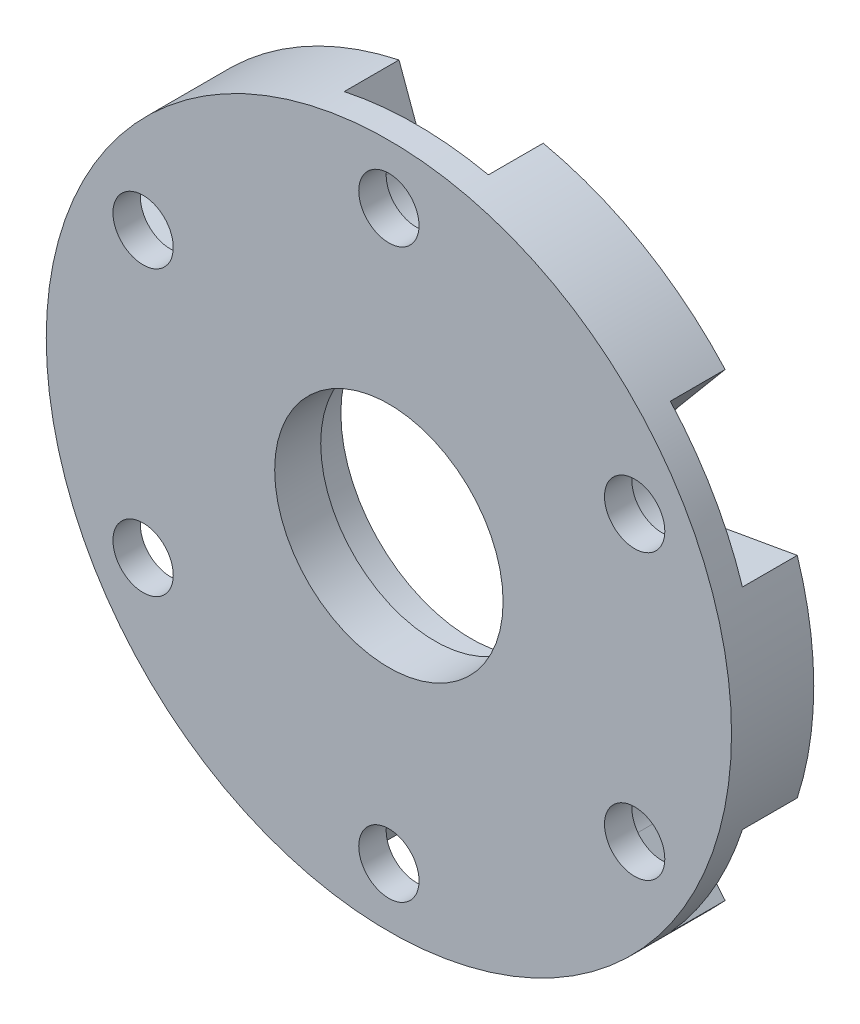
SolidWorks part; units mm, degrees
material "6061-T6 (SS)"
ref_plane "Front Plane" through (0, 0, 0) normal (0, 0, 1) x (1, 0, 0)
ref_plane "Top Plane" through (0, 0, 0) normal (0, 1, 0) x (1, 0, 0)
ref_plane "Right Plane" through (0, 0, 0) normal (1, 0, 0) x (0, 0, -1)
sketch "Sketch Spindle Skeleton" plane through (0, 0, 0) normal (1, 0, 0) x (0, 0, -1)
  line L0 (-108, -9.5) -> (-149, -9.5)
  line L5 (-1000, 0) -> (49000, 0)
  line L6 (0, -9.5) -> (0, 9.5)
  line L13 (0, 9.5) -> (-46.4, 9.5)
  line L26 (-46.4, 9.5) -> (-46.4, 14)
  line L27 (-46.4, 14) -> (-108, 14)
  line L32 (-108, 14) -> (-108, 9.5)
  line L34 (-165, 7) -> (-165, -7)
  line L36 (-108, -9.5) -> (-108, -14)
  line L37 (-108, -14) -> (-46.4, -14)
  line L38 (-46.4, -14) -> (-46.4, -9.5)
  line L39 (0, -9.5) -> (-46.4, -9.5)
  line L40 (-22.625, 37.5) -> (-13.625, 37.5)
  line L41 (-124.6, 22.6187) -> (-108, 22.6187)
  line L42 (-124.6, 22.6187) -> (-124.6, -22.6187)
  line L43 (-124.6, -22.6187) -> (-108, -22.6187)
  line L44 (-108, 22.6187) -> (-108, -22.6187)
  line L45 (-124.6, 22.6187) -> (-108, -22.6187) construction
  line L46 (-124.6, -22.6187) -> (-108, 22.6187) construction
  line L47 (-29.8, 22.6187) -> (-46.4, 22.6187)
  line L48 (-29.8, 22.6187) -> (-29.8, -22.6187)
  line L49 (-29.8, -22.6187) -> (-46.4, -22.6187)
  line L50 (-46.4, 22.6187) -> (-46.4, -22.6187)
  line L51 (-29.8, 22.6187) -> (-46.4, -22.6187) construction
  line L52 (-29.8, -22.6187) -> (-46.4, 22.6187) construction
  line L59 (-13.625, 37.5) -> (-13.625, -37.5)
  line L60 (-13.625, -37.5) -> (-22.625, -37.5)
  line L61 (-22.625, -22.6187) -> (-26.625, -22.6187)
  line L62 (-26.625, -22.6187) -> (-26.625, -12.5)
  line L63 (-26.625, -12.5) -> (-22.625, -12.5)
  line L64 (-22.625, -12.5) -> (-22.625, 12.5)
  line L65 (-22.625, 12.5) -> (-26.625, 12.5)
  line L66 (-26.625, 12.5) -> (-26.625, 22.6187)
  line L67 (-26.625, 22.6187) -> (-22.625, 22.6187)
  line L68 (-22.625, 22.6187) -> (-22.625, 37.5)
  line L69 (-22.625, -22.6187) -> (-22.625, -37.5)
  line L71 (-136.284, 37.5) -> (-23.625, 37.5)
  line L72 (-136.284, 37.5) -> (-136.284, -37.5)
  line L73 (-136.284, -37.5) -> (-23.625, -37.5)
  line L74 (-23.625, 37.5) -> (-23.625, -37.5)
  line L75 (-136.284, 37.5) -> (-23.625, -37.5) construction
  line L76 (-136.284, -37.5) -> (-23.625, 37.5) construction
  line L77 (-149, -9.5) -> (-149, -7)
  line L78 (-149, -7) -> (-165, -7)
  line L79 (-108, 9.5) -> (-149, 9.5)
  line L80 (-149, 7) -> (-165, 7)
  line L81 (-149, 9.5) -> (-149, 7)
  line L82 (-128.5, 9.5) -> (-128.5, -9.5) construction
  line L83 (-23.2, 9.5) -> (-23.2, -9.5) construction
  line L96 (-136.284, 37.5) -> (-145.284, 37.5)
  line L98 (-136.284, -37.5) -> (-145.284, -37.5)
  line L99 (-145.284, 37.5) -> (-145.284, -37.5)
  line L110 (-136.284, 37.5) -> (-136.284, -37.5)
  point P3 (0, 0)
  point P18 (-116.3, 0)
  point P24 (-38.1, 0)
  point P29 (-79.9545, 0)
  point P48 (-13.625, 31.0593)
  point P70 (-145.284, 31.0593)
revolve "Main Revolve" add sketch "Sketch Spindle Skeleton" angle 360 about L5 region at (0, 23.2707, 18.318) region at (0, 17.5594, 25.125)
sketch "Sketch Center Cut" plane through (0, 0, 22.625) normal (0, 0, 1) x (1, 0, 0)
  circle A0 centre (0, 0) radius 12.5 construction
  circle A1 centre (0, 0) radius 12.5 construction
  circle A2 centre (0, 0) radius 12.5
  dimension "D1" = 25
extrude "Cut Center" cut sketch "Sketch Center Cut" against normal through all
hole_wizard "CBORE for M6 SHCS1" positions "Hole wizard sketch 1" profile "Hole wizard sketch 2" counterbore size "M6" standard "ANSI Metric" end condition through all
sketch "Hole wizard sketch 1" plane through (0, 0, 13.625) normal (0, 0, -1) x (-1, 0, 0)
  point P0 (0, 31.0593)
sketch "Hole wizard sketch 2" plane through (0, 31.0593, 13.625) normal (1, 0, 0) x (0, 1, 0)
  line L0 (0, 0) -> (0, 13)
  line L1 (0, 13) -> (3.3, 13)
  line L3 (3.3, 13) -> (3.3, 6)
  line L4 (3.3, 6) -> (5.5, 6)
  line L5 (5.5, 6) -> (5.5, 0)
  line L7 (5.5, 0) -> (0, 0)
  line L11 (0, -6.35) -> (0, 107.95) construction
  dimension "Thru Hole Dia." = 6.6
  dimension "Thru Hole Depth" = 13
  dimension "C'Bore Dia." = 11
  dimension "C'Bore Depth" = 6
pattern_circular "CirPattern1" count 6 over 360 about axis through (0, 0, 13.625) along (0, 0, 1) of "CBORE for M6 SHCS1"
sketch "Sketch1" plane through (0, 0, 13.625) normal (0, 0, -1) x (-1, 0, 0)
  circle A0 centre (0, 0) radius 14.2558
  dimension "D1" = 28.5115
extrude "Cut-Extrude1" cut sketch "Sketch1" against normal blind 3.9624
sketch "Sketch2" plane through (0, 0, 13.625) normal (0, 0, -1) x (-1, 0, 0)
  line L0 (-5.1683, 29.1782) -> (-7.8915, 36.6602)
  line L1 (0, 31.0593) -> (0, 37.5) construction
  line L2 (5.1683, 29.1782) -> (7.8915, 36.6602)
  line L3 (22.6849, 19.065) -> (27.8029, 25.1644)
  line L4 (27.8533, 10.1132) -> (35.6945, 11.4959)
  line L5 (27.8533, -10.1132) -> (35.6945, -11.4959)
  line L6 (22.6849, -19.065) -> (27.8029, -25.1644)
  line L7 (5.1683, -29.1782) -> (7.8915, -36.6602)
  line L8 (-5.1683, -29.1782) -> (-7.8915, -36.6602)
  line L9 (-22.6849, -19.065) -> (-27.8029, -25.1644)
  line L10 (-27.8533, -10.1132) -> (-35.6945, -11.4959)
  line L11 (-27.8533, 10.1132) -> (-35.6945, 11.4959)
  line L12 (-22.6849, 19.065) -> (-27.8029, 25.1644)
  circle A0 centre (0, 31.0593) radius 5.5 construction
  circle A1 centre (0, 0) radius 37.5 construction
  arc A2 (-5.1683, 29.1782) -> (5.1683, 29.1782) centre (0, 31.0593) ccw
  circle A3 centre (0, 0) radius 37.5
  arc A4 (22.6849, 19.065) -> (27.8533, 10.1132) centre (26.8982, 15.5297) ccw
  arc A5 (27.8533, -10.1132) -> (22.6849, -19.065) centre (26.8982, -15.5297) ccw
  arc A6 (5.1683, -29.1782) -> (-5.1683, -29.1782) centre (0, -31.0593) ccw
  arc A7 (-22.6849, -19.065) -> (-27.8533, -10.1132) centre (-26.8982, -15.5297) ccw
  arc A8 (-27.8533, 10.1132) -> (-22.6849, 19.065) centre (-26.8982, 15.5297) ccw
  point P37 (0, 0)
  circle M3 centre (-26.8982, 15.5297) radius 5.5
  circle M4 centre (-26.8982, -15.5297) radius 5.5
  circle M5 centre (0, -31.0593) radius 5.5
  circle M6 centre (26.8982, -15.5297) radius 5.5
  circle M7 centre (26.8982, 15.5297) radius 5.5
  circle M8 centre (0, 31.0593) radius 5.5
  circle M9 centre (0, 0) radius 37.5
  dimension "D1" = 20
  dimension "D2" = 6
extrude "Cut-Extrude2" cut sketch "Sketch2" against normal up to surface (6 mm away) contours M8 | L1 L2 M8 M9 | L1 A3 L0 M8 | L4 L3 M7 M9 | M7 | L6 L5 M6 M9 | M6 | M5 | L8 L7 M5 M9 | L10 L9 M4 M9 | M4 | L12 L11 M3 M9 | A3 M3 region at (4.3779, 34.1248, 13.625) region at (4.7535, 35.3844, 13.625) region at (-4.7535, 35.3844, 13.625) region at (25.3963, 21.9868, 13.625) region at (26.8982, 15.5297, 13.625) region at (-32.3037, 18.6505, 13.625) region at (31.7393, -11.0005, 13.625) region at (-26.8982, 15.5297, 13.625) region at (26.8982, -15.5297, 13.625) region at (6.3623, -32.9803, 13.625) region at (-32.3037, -18.6505, 13.625) region at (0, -31.0593, 13.625) region at (-26.8982, -15.5297, 13.625) up to face at (23.5982, -15.5297, 19.625)
sketch "Sketch3" plane through (0, 0, 26.625) normal (0, 0, 1) x (1, 0, 0)
  circle A0 centre (0, 0) radius 22.6187
  dimension "D1" = 45.2374
extrude "Cut-Extrude3" cut sketch "Sketch3" against normal up to surface (4 mm away) up to face at (30.1982, 15.5297, 22.625)
